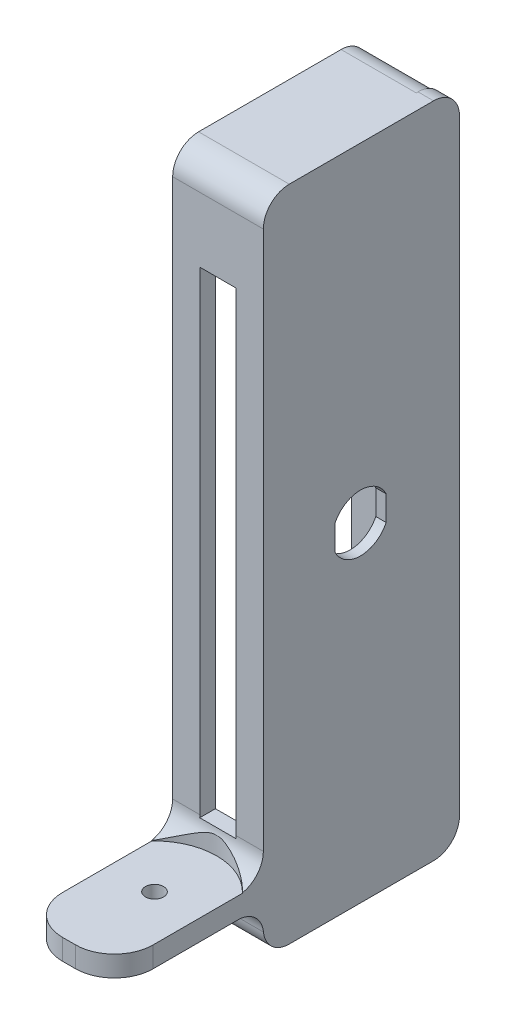
SolidWorks part; units mm, degrees
material "Titanium Ti-8Mn, Annealed"
ref_plane "Front Plane" through (0, 0, 0) normal (0, 0, 1) x (1, 0, 0)
ref_plane "Top Plane" through (0, 0, 0) normal (0, 1, 0) x (1, 0, 0)
ref_plane "Right Plane" through (0, 0, 0) normal (1, 0, 0) x (0, 0, -1)
sketch "Sketch3" plane through (0, 0, 0) normal (1, 0, 0) x (0, 0, -1)
  line L1 (-37.5, -127) -> (37.5, -127)
  line L2 (-37.5, -127) -> (-37.5, 127)
  line L3 (-37.5, 127) -> (37.5, 127)
  line L4 (37.5, -127) -> (37.5, 127)
  line L5 (-37.5, -127) -> (37.5, 127) construction
  line L6 (-37.5, 127) -> (37.5, -127) construction
  point P0 (0, 0)
  dimension "D1" = 254
  dimension "D2" = 75
extrude "Boss-Extrude2" add sketch "Sketch3" along normal blind 35
shell "Shell2" thickness 6 removed face at (35, 0, 0)
sketch "Sketch4" plane through (6, 0, 0) normal (1, 0, 0) x (0, 0, -1)
  line L1 (12.9, -5.4397) -> (12.9, 5.4397)
  line L3 (-12.6, -6.1025) -> (-12.6, 6.1025)
  arc A0 (-12.6, -6.1025) -> (12.9, -5.4397) centre (0, 0) ccw
  arc A1 (12.9, 5.4397) -> (-12.6, 6.1025) centre (0, 0) ccw
  point P9 (-12.6, 0)
  dimension "D1" = 12.9
  dimension "D2" = 14
extrude "Cut-Extrude1" cut sketch "Sketch4" against normal blind 2
sketch "Sketch5" plane through (4, 0, 0) normal (1, 0, 0) x (0, 0, -1)
  line L1 (9.9, -4.7948) -> (9.9, 4.7948)
  line L3 (-9.9, -4.7948) -> (-9.9, 4.7948)
  arc A1 (9.9, 4.7948) -> (-9.9, 4.7948) centre (0, 0) ccw
  arc A2 (-9.9, -4.7948) -> (9.9, -4.7948) centre (0, 0) ccw
  point P11 (-9.9, 0)
extrude "Cut-Extrude2" cut sketch "Sketch5" against normal through all
sketch "Sketch6" plane through (0, 0, 37.5) normal (0, 0, 1) x (1, 0, 0)
  line L0 (17.5, -127) -> (17.5, -92) construction
  line L1 (35, -127) -> (0, -127) construction
  line L2 (17.5, -92) -> (10.5, -92) construction
  line L3 (10.5, -92) -> (10.5, 92)
  line L4 (10.5, 92) -> (24.5, 92)
  line L5 (24.5, 92) -> (24.5, -92)
  line L6 (24.5, -92) -> (10.5, -92)
  line L7 (35, 127) -> (0, 127) construction
  dimension "D1" = 35
  dimension "D2" = 35
extrude "Cut-Extrude3" cut sketch "Sketch6" against normal through all
fillet "Fillet1" radius 10 4 edges at (17.5, -127, 37.5) (17.5, -127, -37.5) (17.5, 127, -37.5) (17.5, 127, 37.5)
fillet "Fillet2" radius 5 4 edges at (20.5, -121, -31.5) (20.5, -121, 31.5) (20.5, 121, -31.5) (20.5, 121, 31.5)
ref_plane "Plane1" through (0, 0, 7.5) normal (0, 0, 1) x (1, 0, 0)
sketch "Sketch12" plane through (35, 0, 0) normal (1, 0, 0) x (0, 0, -1)
  line L2 (-95, -109) -> (-37.5, -109)
  line L3 (-37.5, 117) -> (-37.5, -117) construction
  line L6 (-37.5, -109) -> (-37.5, -101)
  line L7 (-37.5, -101) -> (-95, -101)
  line L8 (-95, -101) -> (-95, -109)
extrude "Boss-Extrude4" add sketch "Sketch12" against normal up to surface (35 mm away) up to face at (0, 0, 0)
fillet "Fillet5" radius 10 2 edges at (17.5, -109, 37.5) (17.5, -101, 37.5)
fillet "Fillet6" radius 15 2 edges at (0, -105, 95) (35, -105, 95)
sketch "Sketch14" plane through (0, -101, 0) normal (0, 1, 0) x (1, 0, 0)
  line L0 (0, 0) -> (0, -37.5) construction
  line L1 (0, -37.5) -> (0, -62) construction
  line L2 (0, -47.5) -> (0, -80) construction
  line L3 (0, -62) -> (17.5, -62) construction
  circle A0 centre (17.5, -62) radius 4
hole_wizard "M8x1.0 Tapped Hole1" positions "3DSketch1" profile "Sketch15" tap size "M8x1.0" standard "ANSI Metric"
sketch3d "3DSketch1"
  point P0 (17.5, -101, 62)
sketch "Sketch15" plane through (17.5, -101, 62) normal (1, 0, 0) x (0, 0, 1)
  line L0 (0, 0) -> (0, 10.103)
  line L1 (0, 10.103) -> (3.5, 8)
  line L2 (3.5, 8) -> (3.5, 0)
  line L5 (3.5, 0) -> (0, 0)
  line L10 (0, 10.103) -> (-3.5, 8) construction
  line L11 (0, -6.35) -> (0, 107.95) construction
  dimension "Tap Drill Dia." = 7
  dimension "Tap Drill Depth" = 8
  dimension "Drill Angle" = 118
cosmetic thread "Hole Thread1" parameters "D1"=8, "D2"=8
sketch "Sketch16" plane through (0, -101, 0) normal (0, 1, 0) x (1, 0, 0)
  circle A0 centre (17.5, -62) radius 24
extrude "Cut-Extrude4" cut sketch "Sketch16" along normal blind 91
sketch "Sketch17" plane through (35, 0, 0) normal (1, 0, 0) x (0, 0, -1)
  line L8 (-26.8069, -127) -> (28.1931, -127)
  line L9 (38.1931, -117) -> (38.1931, 117)
  line L10 (28.1931, 127) -> (-26.8069, 127)
  line L11 (-36.8069, 116.9979) -> (-36.7568, -118)
  arc A2 (-36.7568, -118) -> (-26.8069, -127) centre (-26.8069, -117) ccw
  arc A9 (28.1931, -127) -> (38.1931, -117) centre (28.1931, -117) ccw
  arc A10 (38.1931, 117) -> (28.1931, 127) centre (28.1931, 117) ccw
  arc A11 (-26.8069, 127) -> (-36.8069, 116.9979) centre (-26.8069, 117) ccw
extrude "Boss-Extrude5" add sketch "Sketch17" against normal blind 6
ref_plane "Plane2" through (17.5, 0, 0) normal (-1, 0, 0) x (0, 0, 1)
mirror "Mirror1" about plane through (17.5, 0, 0) normal (-1, 0, 0) of "Cut-Extrude2", "Cut-Extrude1"
sketch "Sketch18" plane through (0, 0, 0) normal (-1, 0, 0) x (0, 0, 1)
  line L0 (-27.5, -127) -> (27.5, -127)
  line L3 (27.5, 127) -> (-27.5, 127)
  line L4 (-37.5, 117) -> (-37.5, -117)
  line L5 (27.5, 121) -> (-27.5, 121)
  line L6 (-31.5, 117) -> (-31.5, -117)
  line L7 (-27.5, -121) -> (27.5, -121)
  line L8 (31.5, 117) -> (31.5, -117)
  line L9 (0, 121) -> (0, 92.6111) construction
  arc A1 (-27.5, 127) -> (-37.5, 117) centre (-27.5, 117) ccw
  arc A2 (-37.5, -117) -> (-27.5, -127) centre (-27.5, -117) ccw
  arc A3 (27.5, 127) -> (37.5, 117) centre (27.5, 117) cw
  arc A4 (27.5, 121) -> (31.5, 117) centre (27.5, 117) cw
  arc A5 (-27.5, 121) -> (-31.5, 117) centre (-27.5, 117) ccw
  arc A6 (-31.5, -117) -> (-27.5, -121) centre (-27.5, -117) ccw
  arc A7 (31.5, -117) -> (27.5, -121) centre (27.5, -117) cw
  dimension "D1" = 6
extrude "Cut-Extrude5" cut sketch "Sketch18" against normal up to surface (29 mm away)
